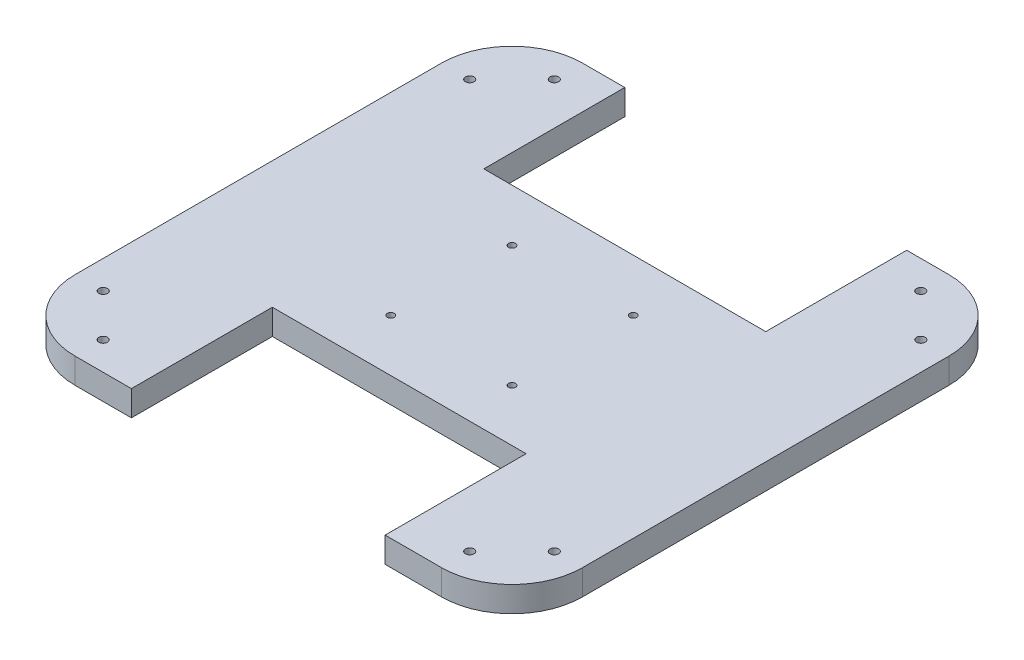
SolidWorks part; units mm, degrees
ref_plane "Front Plane" through (0, 0, 0) normal (0, 0, 1) x (1, 0, 0)
ref_plane "Top Plane" through (0, 0, 0) normal (0, 1, 0) x (1, 0, 0)
ref_plane "Right Plane" through (0, 0, 0) normal (1, 0, 0) x (0, 0, -1)
sketch "Sketch1" plane through (0, 0, 0) normal (0, 1, 0) x (1, 0, 0)
  line L1 (-65, -90) -> (65, -90)
  line L2 (-90, -65) -> (-90, 65)
  line L3 (-65, 90) -> (65, 90)
  line L4 (90, -65) -> (90, 65)
  arc A0 (-90, 65) -> (-65, 90) centre (-65, 65) cw
  arc A1 (65, 90) -> (90, 65) centre (65, 65) cw
  arc A2 (90, -65) -> (65, -90) centre (65, -65) cw
  arc A3 (-65, -90) -> (-90, -65) centre (-65, -65) cw
  point P4 (-90, 0)
  point P6 (0, 90)
  dimension "D3" = 25
  dimension "D1" = 180
  dimension "D2" = 180
extrude "Plate" add sketch "Sketch1" along normal blind 9
sketch "Sketch3" plane through (0, 9, 0) normal (0, 1, 0) x (1, 0, 0)
  line L0 (-65, 90) -> (-65, -90) construction
  line L1 (65, 90) -> (65, -90) construction
  line L2 (-90, 65) -> (90, 65) construction
  line L3 (-90, -65) -> (90, -65) construction
  circle A0 centre (-65, 80) radius 1.525
  circle A1 centre (-80, 65) radius 1.525
  circle A2 centre (80, 65) radius 1.525
  circle A3 centre (80, -65) radius 1.525
  circle A4 centre (65, 80) radius 1.525
  circle A5 centre (65, -80) radius 1.525
  circle A6 centre (-65, -80) radius 1.525
  circle A7 centre (-80, -65) radius 1.525
  dimension "D1" = 3.05
  dimension "D2" = 15
  dimension "D3" = 15
  dimension "D4" = 15
  dimension "D5" = 15
  dimension "D6" = 15
  dimension "D7" = 15
  dimension "D8" = 15
  dimension "D9" = 15
extrude "Hex Holes" cut sketch "Sketch3" against normal through all
sketch "Sketch4" plane through (0, 9, 0) normal (0, 1, 0) x (1, 0, 0)
  line L0 (-90, -65) -> (-90, 65) construction
  line L1 (-65, -90) -> (65, -90) construction
  circle A0 centre (-21.5, 21.5) radius 1.25
  circle A1 centre (21.5, 21.5) radius 1.25
  circle A2 centre (21.5, -21.5) radius 1.25
  circle A3 centre (-21.5, -21.5) radius 1.25
  dimension "D1" = 2.5
  dimension "D2" = 43
  dimension "D3" = 43
  dimension "D4" = 68.5
  dimension "D5" = 68.5
extrude "LiDAR Holes" cut sketch "Sketch4" against normal through all
sketch "Sketch5" plane through (0, 9, 0) normal (0, 1, 0) x (1, 0, 0)
  line L0 (-65, 90) -> (65, 90) construction
  line L1 (50, 90) -> (-50, 90)
  line L2 (50, 90) -> (50, 40)
  line L3 (50, 40) -> (-50, 40)
  line L4 (-50, 90) -> (-50, 40)
  line L5 (-65, -90) -> (65, -90) construction
  line L6 (45, -90) -> (-45, -90)
  line L7 (45, -90) -> (45, -40)
  line L8 (45, -40) -> (-45, -40)
  line L9 (-45, -90) -> (-45, -40)
  point P6 (0, 90)
  point P7 (0, 90)
  point P14 (0, -90)
  point P15 (0, -90)
  dimension "D1" = 100
  dimension "D2" = 50
  dimension "D3" = 50
  dimension "D4" = 90
extrude "Cut-Extrude1" cut sketch "Sketch5" against normal through all
